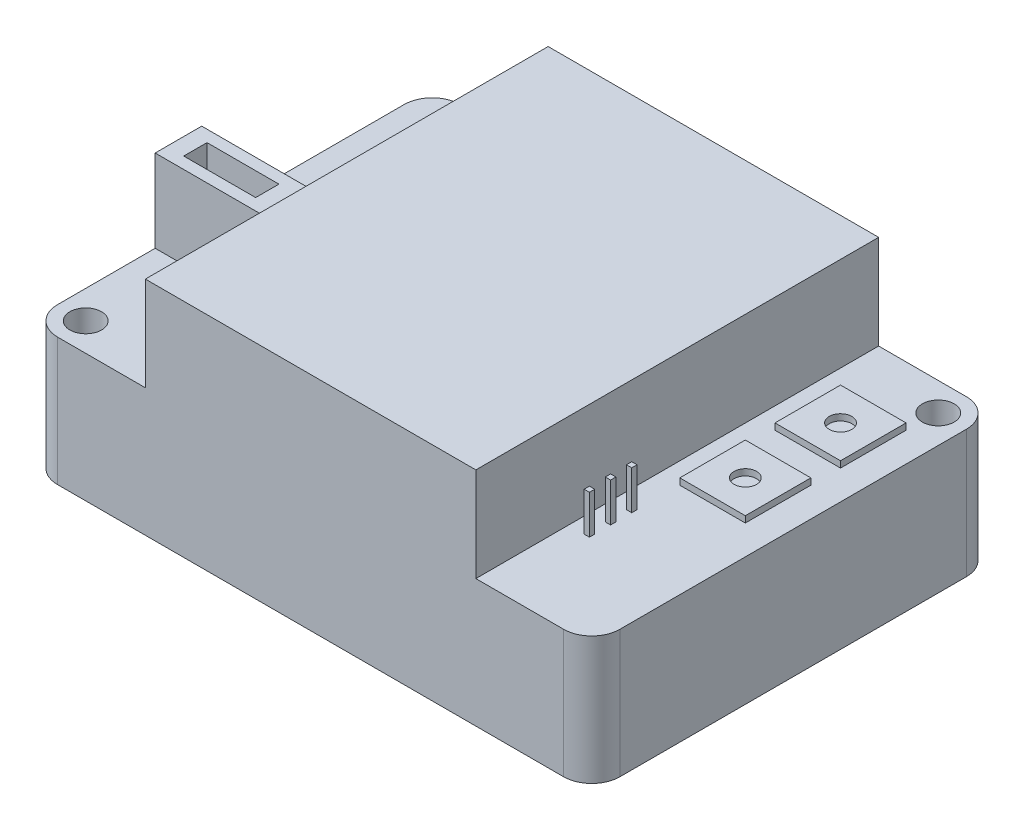
SolidWorks part; units mm, degrees
ref_plane "Front Plane" through (0, 0, 0) normal (0, 0, 1) x (1, 0, 0)
ref_plane "Top Plane" through (0, 0, 0) normal (0, 1, 0) x (1, 0, 0)
ref_plane "Right Plane" through (0, 0, 0) normal (1, 0, 0) x (0, 0, -1)
sketch "Sketch1" plane through (0, 0, 0) normal (0, 0, 1) x (1, 0, 0)
  line L1 (0, 0) -> (67.5157, 0)
  line L2 (0, 0) -> (0, 15.3416)
  line L3 (13.9167, 26.6446) -> (53.5991, 26.6446)
  line L4 (67.5157, 0) -> (67.5157, 15.3416)
  line L7 (0, 15.3416) -> (13.9167, 15.3416)
  line L8 (13.9167, 26.6446) -> (13.9167, 15.3416)
  line L11 (67.5157, 15.3416) -> (53.5991, 15.3416)
  line L12 (53.5991, 26.6446) -> (53.5991, 15.3416)
  dimension "D1" = 67.5157
  dimension "D2" = 15.3416
  dimension "D3" = 26.6446
  dimension "D4" = 13.9167
extrude "Boss-Extrude1" add sketch "Sketch1" against normal blind 48.3616
fillet "Fillet1" radius 3.3782 4 edges at (0, 7.6708, -48.3616) (67.5157, 7.6708, -48.3616) (67.5157, 7.6708, 0) (0, 7.6708, 0)
sketch "Sketch2" plane through (0, 15.3416, 0) normal (0, 1, 0) x (1, 0, 0)
  circle A0 centre (3.3782, 3.3782) radius 1.905
  circle A1 centre (64.1375, 44.9834) radius 1.905
  dimension "D1" = 3.81
extrude "Cut-Extrude1" cut sketch "Sketch2" against normal through all
sketch "Sketch3" plane through (0, 15.3416, 0) normal (0, 1, 0) x (1, 0, 0)
  line L0 (3.5154, 48.3616) -> (3.5154, 0) construction
  line L1 (13.9167, 48.3616) -> (3.3782, 48.3616) construction
  line L2 (13.9167, 0) -> (3.3782, 0) construction
  line L3 (0, 44.9834) -> (0, 3.3782) construction
  line L4 (33.7579, 48.3616) -> (33.7579, 0) construction
  line L5 (53.5991, 48.3616) -> (13.9167, 48.3616) construction
  line L6 (53.5991, 0) -> (13.9167, 0) construction
  line L7 (56.1315, 21.9532) -> (56.1315, 29.8221)
  line L8 (3.5154, 33.3832) -> (11.3843, 33.3832)
  line L9 (3.5154, 33.3832) -> (3.5154, 41.2521)
  line L10 (3.5154, 41.2521) -> (11.3843, 41.2521)
  line L11 (11.3843, 33.3832) -> (11.3843, 41.2521)
  line L12 (3.5154, 21.9532) -> (11.3843, 21.9532)
  line L13 (3.5154, 21.9532) -> (3.5154, 29.8221)
  line L14 (3.5154, 29.8221) -> (11.3843, 29.8221)
  line L15 (11.3843, 21.9532) -> (11.3843, 29.8221)
  line L16 (64.0004, 33.3832) -> (56.1315, 33.3832)
  line L17 (64.0004, 21.9532) -> (56.1315, 21.9532)
  line L18 (64.0004, 21.9532) -> (64.0004, 29.8221)
  line L19 (64.0004, 29.8221) -> (56.1315, 29.8221)
  line L20 (64.0004, 33.3832) -> (64.0004, 41.2521)
  line L21 (56.1315, 33.3832) -> (56.1315, 41.2521)
  line L22 (64.0004, 41.2521) -> (56.1315, 41.2521)
  line L23 (3.5154, 33.3832) -> (11.3843, 41.2521) construction
  line L24 (3.5154, 21.9532) -> (11.3843, 29.8221) construction
  circle A0 centre (7.4498, 37.3177) radius 1.3525
  circle A1 centre (7.4498, 25.8877) radius 1.3525
  circle A2 centre (60.0659, 25.8877) radius 1.3525
  circle A3 centre (60.0659, 37.3177) radius 1.3526
  dimension "D5" = 2.7051
  dimension "D1" = 3.5154
  dimension "D2" = 7.1095
  dimension "D3" = 3.5611
  dimension "D4" = 7.8689
extrude "Boss-Extrude2" add sketch "Sketch3" along normal blind 0.762
sketch "Sketch4" plane through (0, 15.3416, 0) normal (0, 1, 0) x (1, 0, 0)
  line L0 (3.5154, 21.9532) -> (11.3843, 21.9532) construction
  line L1 (0, 15.0952) -> (12.7, 15.0952)
  line L2 (0, 15.0952) -> (0, 20.6832)
  line L3 (0, 20.6832) -> (12.7, 20.6832)
  line L4 (12.7, 15.0952) -> (12.7, 20.6832)
  line L5 (0, 15.0952) -> (12.7, 20.6832) construction
  line L6 (0, 20.6832) -> (12.7, 15.0952) construction
  line L7 (2.032, 16.4922) -> (10.668, 16.4922)
  line L8 (2.032, 16.4922) -> (2.032, 19.2862)
  line L9 (2.032, 19.2862) -> (10.668, 19.2862)
  line L10 (10.668, 16.4922) -> (10.668, 19.2862)
  line L11 (2.032, 16.4922) -> (10.668, 19.2862) construction
  line L12 (2.032, 19.2862) -> (10.668, 16.4922) construction
  line L13 (0, 44.9834) -> (0, 3.3782) construction
  point P0 (6.35, 17.8892)
  point P5 (6.35, 17.8892)
  dimension "D1" = 1.27
  dimension "D2" = 5.588
  dimension "D3" = 2.794
  dimension "D4" = 8.636
  dimension "D5" = 12.7
extrude "Boss-Extrude3" add sketch "Sketch4" along normal blind 9.906
sketch "Sketch5" plane through (0, 15.3416, 0) normal (0, 1, 0) x (1, 0, 0)
  line L0 (64.1375, 0) -> (53.5991, 0) construction
  line L1 (55.4787, 16.2027) -> (56.1137, 16.2027)
  line L2 (55.4787, 16.2027) -> (55.4787, 16.8377)
  line L3 (55.4787, 16.8377) -> (56.1137, 16.8377)
  line L4 (56.1137, 16.2027) -> (56.1137, 16.8377)
  line L5 (55.4787, 16.2027) -> (56.1137, 16.8377) construction
  line L6 (55.4787, 16.8377) -> (56.1137, 16.2027) construction
  line L7 (55.4787, 13.6627) -> (56.1137, 13.6627)
  line L8 (55.4787, 13.6627) -> (55.4787, 14.2977)
  line L9 (55.4787, 14.2977) -> (56.1137, 14.2977)
  line L10 (56.1137, 13.6627) -> (56.1137, 14.2977)
  line L11 (55.4787, 13.6627) -> (56.1137, 14.2977) construction
  line L12 (55.4787, 14.2977) -> (56.1137, 13.6627) construction
  line L13 (55.4787, 11.1227) -> (56.1137, 11.1227)
  line L14 (55.4787, 11.1227) -> (55.4787, 11.7577)
  line L15 (55.4787, 11.7577) -> (56.1137, 11.7577)
  line L16 (56.1137, 11.1227) -> (56.1137, 11.7577)
  line L17 (55.4787, 11.1227) -> (56.1137, 11.7577) construction
  line L18 (55.4787, 11.7577) -> (56.1137, 11.1227) construction
  line L19 (53.5991, 48.3616) -> (53.5991, 0) construction
  point P0 (55.7962, 16.5202)
  point P5 (55.7962, 13.9802)
  point P10 (55.7962, 11.4402)
  dimension "D1" = 2.54
  dimension "D2" = 2.54
  dimension "D3" = 0.635
  dimension "D4" = 11.1227
  dimension "D5" = 1.8796
extrude "Boss-Extrude4" add sketch "Sketch5" along normal blind 4.6736
sketch "Sketch6" plane through (0, 15.3416, 0) normal (0, 1, 0) x (1, 0, 0)
  line L0 (2.032, 17.8892) -> (10.668, 17.8892) construction
  line L1 (2.032, 19.2862) -> (2.032, 16.4922) construction
  line L2 (10.668, 16.4922) -> (10.668, 19.2862) construction
  line L3 (4.191, 19.2862) -> (4.191, 16.4922) construction
  line L4 (10.668, 19.2862) -> (2.032, 19.2862) construction
  line L5 (2.032, 16.4922) -> (10.668, 16.4922) construction
  line L6 (8.509, 19.2862) -> (8.509, 16.4922) construction
  line L7 (10.668, 19.2862) -> (2.032, 19.2862) construction
  line L8 (6.35, 19.2862) -> (6.35, 16.4922) construction
  line L9 (2.032, 16.4922) -> (10.668, 16.4922) construction
  line L11 (2.032, 19.2862) -> (2.032, 16.4922) construction
  line L12 (55.4787, 16.2027) -> (56.1137, 16.8377) construction
  line L13 (55.4787, 13.6627) -> (56.1137, 14.2977) construction
  line L14 (55.4787, 11.1227) -> (56.1137, 11.7577) construction
  point P20 (4.191, 17.8892)
  point P21 (6.35, 17.8892)
  point P22 (8.509, 17.8892)
  point P23 (7.4498, 37.3177)
  point P24 (7.4498, 25.8877)
  point P26 (60.0659, 37.3177)
  point P28 (60.0659, 25.8877)
  point P39 (55.7962, 13.9802)
  point P44 (55.7962, 11.4402)
  point P45 (55.7962, 16.5202)
sketch "0_0_Point" plane through (0, 15.3416, 0) normal (0, 1, 0) x (1, 0, 0)
  point P0 (7.4498, 25.8877)
other "0_0"
ref_axis "Axis1" through (7.4498, 25.3416, -25.8877) along (0, -1, 0)
sketch "1_0_Point" plane through (0, 15.3416, 0) normal (0, 1, 0) x (1, 0, 0)
  point P0 (7.4498, 37.3177)
other "1_0"
ref_axis "Axis2" through (7.4498, 25.3416, -37.3177) along (0, -1, 0)
sketch "2_0_Point" plane through (0, 15.3416, 0) normal (0, 1, 0) x (1, 0, 0)
  point P0 (60.0659, 25.8877)
other "2_0"
ref_axis "Axis3" through (60.0659, 25.3416, -25.8877) along (0, -1, 0)
sketch "3_0_Point" plane through (0, 15.3416, 0) normal (0, 1, 0) x (1, 0, 0)
  point P0 (60.0659, 37.3177)
other "3_0"
ref_axis "Axis4" through (60.0659, 25.3416, -37.3177) along (0, -1, 0)
sketch "4_0_Point" plane through (0, 15.3416, 0) normal (0, 1, 0) x (1, 0, 0)
  point P0 (4.191, 17.8892)
other "4_0"
ref_axis "Axis5" through (4.191, 25.3416, -17.8892) along (0, -1, 0)
sketch "4_1_Point" plane through (0, 15.3416, 0) normal (0, 1, 0) x (1, 0, 0)
  point P0 (6.35, 17.8892)
other "4_1"
ref_axis "Axis6" through (6.35, 25.3416, -17.8892) along (0, -1, 0)
sketch "4_2_Point" plane through (0, 15.3416, 0) normal (0, 1, 0) x (1, 0, 0)
  point P0 (8.509, 17.8892)
other "4_2"
ref_axis "Axis7" through (8.509, 25.3416, -17.8892) along (0, -1, 0)
sketch "5_0_Point" plane through (0, 15.3416, 0) normal (0, 1, 0) x (1, 0, 0)
  point P0 (55.7962, 11.4402)
other "5_0"
ref_axis "Axis8" through (55.7962, 25.3416, -11.4402) along (0, -1, 0)
sketch "5_1_Point" plane through (0, 15.3416, 0) normal (0, 1, 0) x (1, 0, 0)
  point P0 (55.7962, 13.9802)
other "5_1"
ref_axis "Axis9" through (55.7962, 25.3416, -13.9802) along (0, -1, 0)
sketch "5_2_Point" plane through (0, 15.3416, 0) normal (0, 1, 0) x (1, 0, 0)
  point P0 (55.7962, 16.5202)
other "5_2"
ref_axis "Axis10" through (55.7962, 25.3416, -16.5202) along (0, -1, 0)
